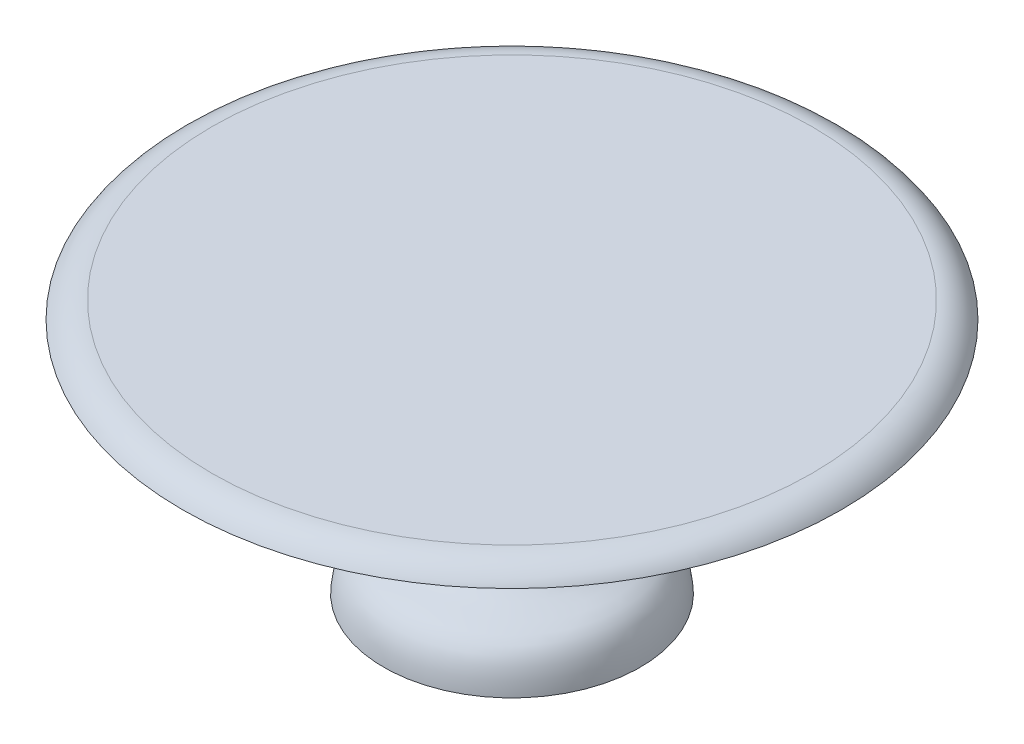
SolidWorks part; units mm, degrees
ref_plane "前基準面" through (0, 0, 0) normal (0, 0, 1) x (1, 0, 0)
ref_plane "上基準面" through (0, 0, 0) normal (0, 1, 0) x (1, 0, 0)
ref_plane "右基準面" through (0, 0, 0) normal (1, 0, 0) x (0, 0, -1)
sketch "草圖2" plane through (0, 0, 0) normal (0, 0, 1) x (1, 0, 0)
  line L0 (0, 0) -> (0, 15) construction
  line L1 (0, 15) -> (-20, 15)
  line L2 (-20, 15) -> (-19.4664, 14)
  line L3 (-19.4664, 14) -> (-4.9493, 14)
  line L12 (-7.5826, 0) -> (0, 0)
  line L13 (0, 0) -> (0, 15)
  spline S0 degree 3 poles (-4.9493, 14) (-3.4395, 11.7087) (-13.6383, 2.4567) (-0.3057, 11.8606) (-3.8884, 1.6439) (-7.3321, 3.0554) (-7.5826, 0) knots 0 0 0 0 0.345472 0.594733 0.813463 1 1 1 1
  point P6 (-4.4259, 15.4175)
  point P8 (-4.9577, 2.9616)
  point P10 (-4.4215, 3.3953)
  point P12 (-5.063, 3.0279)
  point P15 (-3.3183, 16.0522)
  point P17 (-3.9254, 9.1319)
  point P18 (-4.9967, 11.8189)
  point P19 (-2.7079, 8.6065)
  point P20 (-8.5577, 6.4018)
  dimension "D1" = 15
  dimension "D2" = 20
  dimension "D3" = 1
revolve "旋轉1" add sketch "草圖2" angle 360 about L0
fillet "圓角1" radius 2 1 edges at (0, 15, -20)
